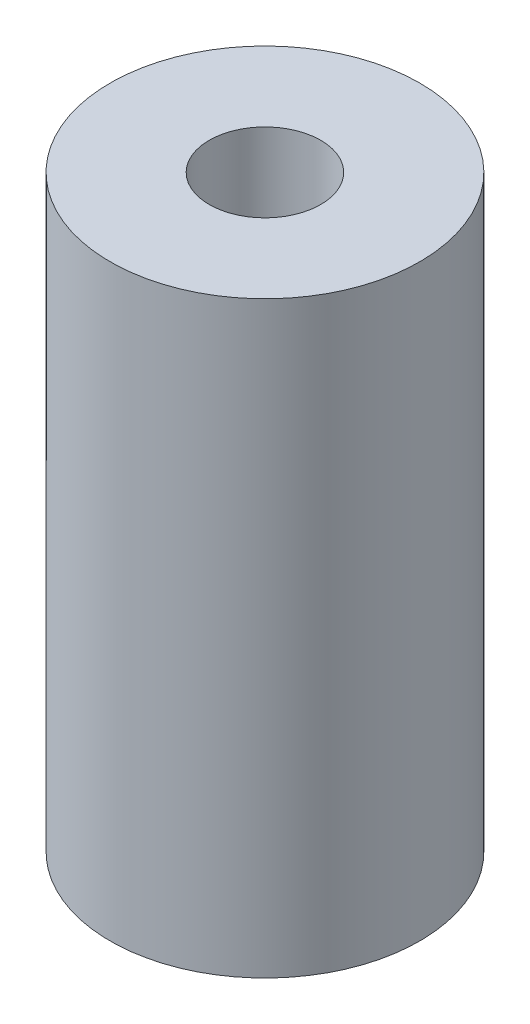
SolidWorks part; units mm, degrees
ref_plane "Front Plane" through (0, 0, 0) normal (0, 0, 1) x (1, 0, 0)
ref_plane "Top Plane" through (0, 0, 0) normal (0, 1, 0) x (1, 0, 0)
ref_plane "Right Plane" through (0, 0, 0) normal (1, 0, 0) x (0, 0, -1)
sketch "Sketch1" plane through (0, 0, 0) normal (0, 0, 1) x (1, 0, 0)
  line L0 (0, 0) -> (0, 5.7533) construction
  line L1 (-0.9, 9.5) -> (-0.9, 4)
  line L2 (-0.9, 4) -> (-1.25, 4)
  line L3 (-1.25, 4) -> (-1.25, 0)
  line L4 (-1.25, 0) -> (-2.5, 0)
  line L5 (-2.5, 0) -> (-2.5, 9.5)
  line L6 (-2.5, 9.5) -> (-0.9, 9.5)
  dimension "D1" = 2.5
  dimension "D2" = 5
  dimension "D3" = 1.8
  dimension "D4" = 5.5
  dimension "D5" = 4
revolve "Revolve1" add sketch "Sketch1" angle 360 about L0
